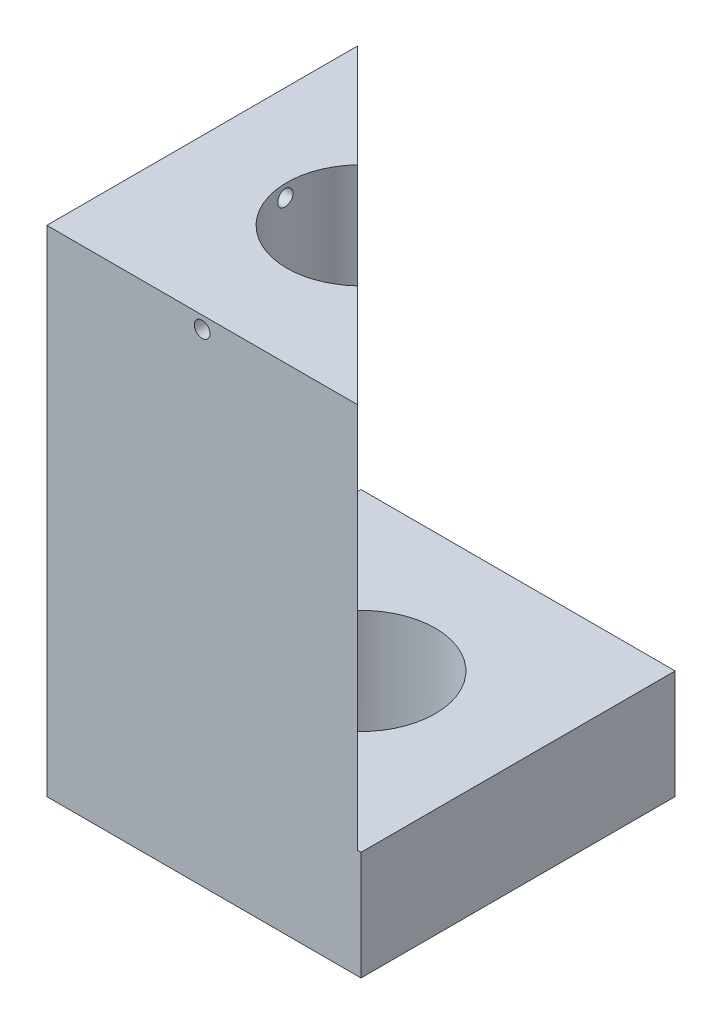
SolidWorks part; units mm, degrees
material "7075-O (SS)"
ref_plane "Front Plane" through (0, 0, 0) normal (0, 0, 1) x (1, 0, 0)
ref_plane "Top Plane" through (0, 0, 0) normal (0, 1, 0) x (1, 0, 0)
ref_plane "Right Plane" through (0, 0, 0) normal (1, 0, 0) x (0, 0, -1)
sketch "Sketch1" plane through (0, 0, 0) normal (0, 1, 0) x (1, 0, 0)
  line L1 (0, 0) -> (12.7, 0)
  line L2 (0, 0) -> (0, 12.7)
  line L3 (0, 12.7) -> (12.7, 12.7)
  line L4 (12.7, 0) -> (12.7, 12.7)
  dimension "D1" = 12.7
  dimension "D2" = 12.7
extrude "Boss-Extrude1" add sketch "Sketch1" along normal blind 20
sketch "Sketch2" plane through (0, 20, 0) normal (0, 1, 0) x (1, 0, 0)
  line L0 (0, 0) -> (12.7, 12.7) construction
  circle A0 centre (6.35, 6.35) radius 3
  dimension "D1" = 6
extrude "Cut-Extrude1" cut sketch "Sketch2" against normal through all
sketch "Sketch3" plane through (0, 20, 0) normal (0, 1, 0) x (1, 0, 0)
  line L0 (0, 12.7) -> (12.7, 0) construction
  line L1 (12.7, 0) -> (12.5563, 0)
  line L2 (12.7, 0) -> (12.7, 12.7) construction
  line L3 (12.7, 12.7) -> (0, 12.7) construction
  line L4 (0, 12.7) -> (12.7, 12.7)
  line L5 (12.7, 12.7) -> (12.7, 0)
  line L6 (0, 0) -> (12.7, 0) construction
  line L7 (12.5563, 0) -> (0, 12.5563)
  line L8 (0, 12.7) -> (0, 0) construction
  line L9 (0, 12.5563) -> (0, 12.7)
  dimension "D1" = 0.2032
extrude "Cut-Extrude2" cut sketch "Sketch3" against normal blind 15.6
hole_wizard "#72 (0.025) Diameter Hole1" positions "3DSketch1" profile "Sketch4" hole size "#72" standard "ANSI Inch" end condition up to next
sketch3d "3DSketch1"
  line L0 (0, 20, -6.2782) -> (0, 19.5, -6.2782) construction
  line L1 (0, 20, -12.5563) -> (0, 20, 0) construction
  line L4 (6.2782, 20, 0) -> (6.2782, 19.5, 0) construction
  line L5 (0, 20, 0) -> (12.5563, 20, 0) construction
  point P11 (6.2782, 19.5, 0)
  point P13 (0, 19.5, -6.2782)
  dimension "D1" = 0.5
sketch "Sketch4" plane through (6.2782, 19.5, 0) normal (1, 0, 0) x (0, -1, 0)
  line L0 (0, 0) -> (0, 3.3509)
  line L1 (0, 3.3509) -> (0.3175, 3.3509)
  line L2 (0.3175, 3.3509) -> (0.3175, 0)
  line L5 (0.3175, 0) -> (0, 0)
  line L11 (0, -6.35) -> (0, 107.95) construction
  dimension "Thru Hole Dia." = 0.635
  dimension "Thru Hole Depth" = 3.3509
